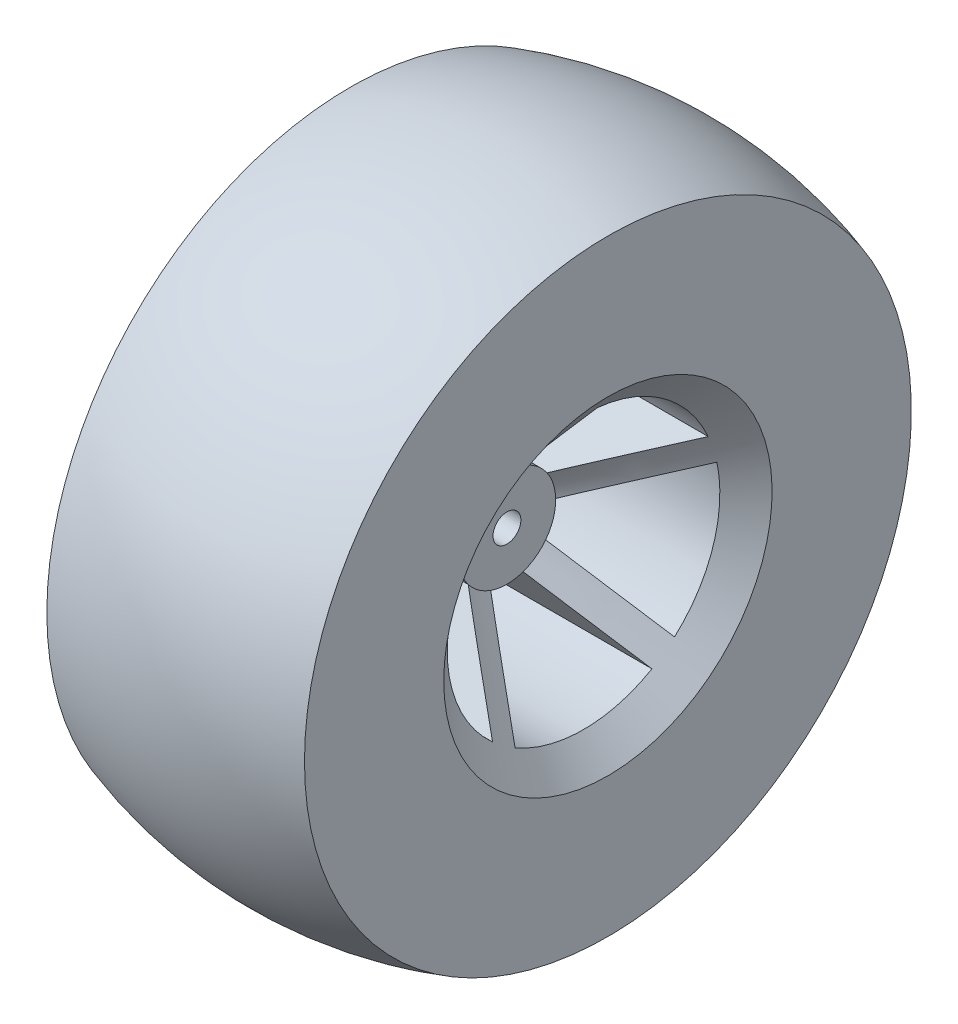
SolidWorks part; units mm, degrees
ref_plane "Front Plane" through (0, 0, 0) normal (0, 0, 1) x (1, 0, 0)
ref_plane "Top Plane" through (0, 0, 0) normal (0, 1, 0) x (1, 0, 0)
ref_plane "Right Plane" through (0, 0, 0) normal (1, 0, 0) x (0, 0, -1)
sketch "Sketch1" plane through (0, 0, 0) normal (0, 1, 0) x (1, 0, 0)
  line L0 (0, -46.5) -> (-98.1265, -46.5) construction
  line L1 (18.5, -43.5767) -> (18.5, -23.5767)
  line L2 (18.5, -23.5767) -> (4, -7)
  line L3 (4, -7) -> (4, -2)
  line L5 (0, -2) -> (0, -46.5)
  line L6 (4, -2) -> (0, -2)
  line L7 (-21.5213, 0) -> (29.4065, 0) construction
  arc A0 (18.5, -43.5767) -> (0, -46.5) centre (0, 13.5) cw
  dimension "D4" = 60
  dimension "D1" = 18.5
  dimension "D2" = 20
  dimension "D3" = 46.5
  dimension "D5" = 5
  dimension "D6" = 4
  dimension "D7" = 2
revolve "Revolve1" add sketch "Sketch1" angle 360 about L7
mirror "Mirror1" about plane through (0, 0, 2) normal (-1, 0, 0) of bodies 101
sketch "Sketch2" plane through (0, 0, 0) normal (1, 0, 0) x (0, 0, -1)
  line L0 (0, 0) -> (0, 19.5767)
  line L1 (0, 0) -> (18.6186, 6.0495)
  line L2 (0, 0) -> (11.5069, -15.8379)
  line L3 (0, 0) -> (-11.5069, -15.8379)
  line L4 (0, 0) -> (-18.6186, 6.0495)
  line L5 (2, 19.4743) -> (2, 2.7528)
  line L6 (2, 2.7528) -> (17.9031, 7.92)
  line L7 (-2, 19.4743) -> (-2, 2.7528)
  line L8 (-2, 2.7528) -> (-17.9031, 7.92)
  line L9 (-19.1392, 4.1158) -> (-3.2361, -1.0515)
  line L10 (-3.2361, -1.0515) -> (-13.0647, -14.5794)
  line L11 (-9.8287, -16.9306) -> (0, -3.4026)
  line L12 (0, -3.4026) -> (9.8287, -16.9306)
  line L13 (13.0647, -14.5794) -> (3.2361, -1.0515)
  line L14 (3.2361, -1.0515) -> (19.1392, 4.1158)
  circle A0 centre (0, 0) radius 19.5767
  circle A1 centre (0, 0) radius 7
  circle A2 centre (0, 0) radius 7 construction
  circle A3 centre (0, 0) radius 23.5767 construction
  dimension "D1" = 4
  dimension "D2" = 72
  dimension "D3" = 72
  dimension "D4" = 72
  dimension "D5" = 72
  dimension "D6" = 4
extrude "Cut-Extrude1" cut sketch "Sketch2" against normal through all both and the other way through all contours A1 L7 A0 L8 | A1 L6 A0 L5 | A1 L9 A0 L10 | A1 L13 A0 L14 | A1 L11 A0 L12 region at (0, 11.3392, -8.2384) region at (0, 11.3392, 8.2384) region at (0, -4.3312, -13.3301) region at (0, -14.0161, 0) region at (0, -4.3312, 13.3301)
